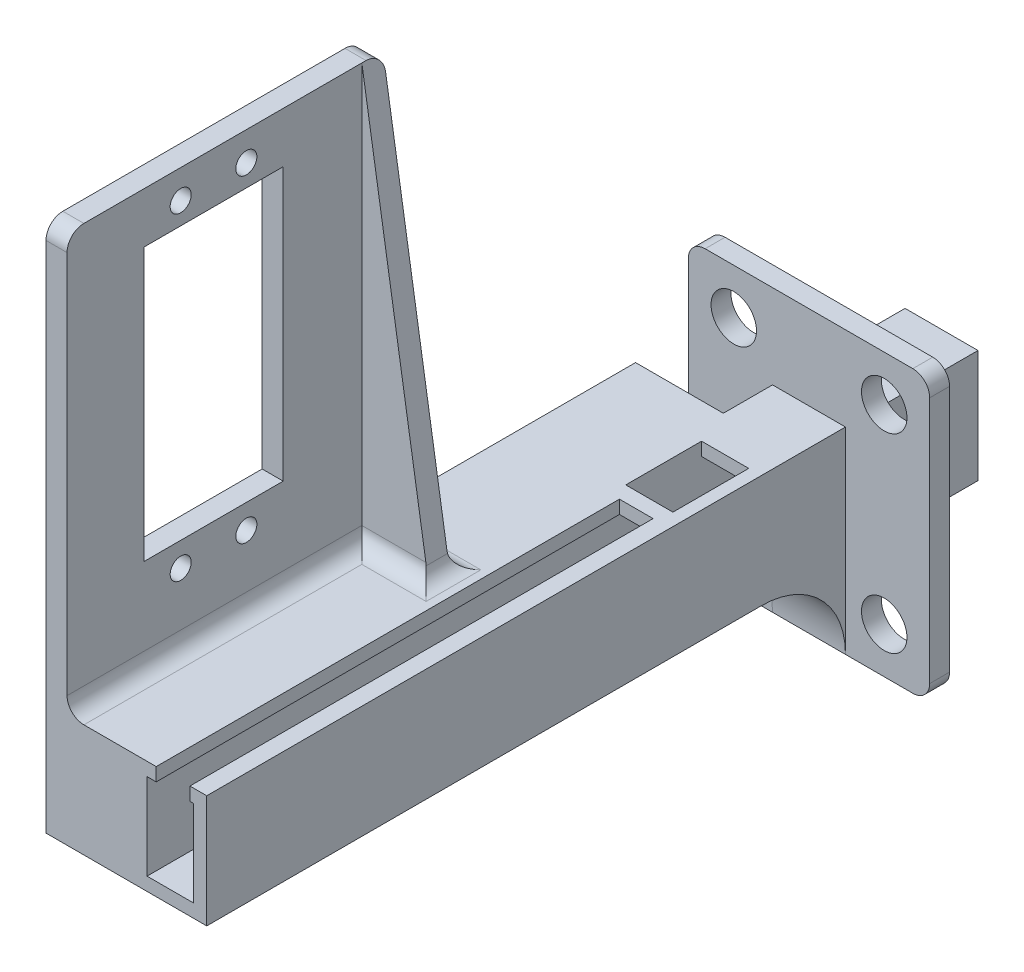
SolidWorks part; units mm, degrees
ref_plane "Front Plane" through (0, 0, 0) normal (0, 0, 1) x (1, 0, 0)
ref_plane "Top Plane" through (0, 0, 0) normal (0, 1, 0) x (1, 0, 0)
ref_plane "Right Plane" through (0, 0, 0) normal (1, 0, 0) x (0, 0, -1)
sketch "Sketch1" plane through (0, 0, 0) normal (0, 0, 1) x (1, 0, 0)
  line L1 (0, 0) -> (7, 0)
  line L2 (0, 0) -> (0, 13)
  line L3 (0, 13) -> (7, 13)
  line L4 (7, 0) -> (7, 13)
  line L5 (-2, -2) -> (9, -2)
  line L6 (-2, -2) -> (-2, 15)
  line L7 (-2, 15) -> (9, 15)
  line L8 (9, -2) -> (9, 15)
  dimension "D1" = 7
  dimension "D2" = 13
  dimension "D3" = 2
  dimension "D4" = 2
  dimension "D5" = 2
  dimension "D6" = 2
extrude "Boss-Extrude1" add sketch "Sketch1" along normal blind 76.2
sketch "Sketch2" plane through (0, 0, 0) normal (0, 0, -1) x (-1, 0, 0)
  line L1 (-9, -2) -> (2, -2)
  line L2 (-9, -2) -> (-9, 15)
  line L3 (-9, 15) -> (2, 15)
  line L4 (2, -2) -> (2, 15)
extrude "Boss-Extrude2" add sketch "Sketch2" along normal blind 2
sketch "Sketch3" plane through (0, -2, 0) normal (0, -1, 0) x (-1, 0, 0)
  line L0 (-9, 2) -> (2, 2) construction
  line L1 (-7, 0) -> (0, 0)
  line L2 (-7, 0) -> (-7, -11)
  line L3 (-7, -11) -> (0, -11)
  line L4 (0, 0) -> (0, -11)
  line L5 (2, -76.2) -> (2, 2) construction
  line L6 (-9, -76.2) -> (-9, 2) construction
  dimension "D1" = 2
  dimension "D2" = 2
  dimension "D3" = 2
  dimension "D4" = 11
extrude "Cut-Extrude1" cut sketch "Sketch3" against normal up to surface (2 mm away) up to face at (3.5, 0, 38.1)
ref_plane "Plane1" through (0, 0, 14.986) normal (0, 0, 1) x (1, 0, 0)
sketch "Sketch4" plane through (0, 0, 14.986) normal (0, 0, 1) x (1, 0, 0)
  line L2 (-2, 15) -> (9, 15)
  line L3 (-2, 15) -> (-2, -2)
  line L4 (-2, -2) -> (9, -2)
  line L5 (9, 15) -> (9, -2)
  line L6 (-12.16, 27.7) -> (19.16, 27.7)
  line L7 (-14.7, 25.16) -> (-14.7, -12.16)
  line L8 (-12.16, -14.7) -> (19.16, -14.7)
  line L9 (21.7, 25.16) -> (21.7, -12.16)
  circle A1 centre (-7.842, 20.842) radius 3.429
  circle A2 centre (14.842, 20.842) radius 3.429
  circle A3 centre (-7.842, -7.842) radius 3.429
  circle A4 centre (14.842, -7.842) radius 3.429
  arc A5 (-12.16, 27.7) -> (-14.7, 25.16) centre (-12.16, 25.16) ccw
  arc A6 (-14.7, -12.16) -> (-12.16, -14.7) centre (-12.16, -12.16) ccw
  arc A7 (19.16, -14.7) -> (21.7, -12.16) centre (19.16, -12.16) ccw
  arc A8 (21.7, 25.16) -> (19.16, 27.7) centre (19.16, 25.16) ccw
  point P3 (0, 0)
  dimension "D3" = 12.7
  dimension "D5" = 6.858
  dimension "D6" = 6.858
  dimension "D7" = 6.858
  dimension "D8" = 6.858
  dimension "D17" = 2.54
  dimension "D1" = 12.7
  dimension "D2" = 12.7
  dimension "D4" = 12.7
  dimension "D9" = 6.858
  dimension "D10" = 6.858
  dimension "D11" = 6.858
  dimension "D12" = 6.858
  dimension "D13" = 6.858
  dimension "D14" = 6.858
  dimension "D15" = 6.858
  dimension "D16" = 6.858
extrude "Boss-Extrude3" add sketch "Sketch4" along normal blind 3
sketch "Sketch6" plane through (0, 15, 0) normal (0, 1, 0) x (1, 0, 0)
  line L0 (9, -17.986) -> (-2, -17.986) construction
  line L1 (0, -30.686) -> (7.112, -30.686)
  line L2 (0, -30.686) -> (0, -42.116)
  line L3 (0, -42.116) -> (7.112, -42.116)
  line L4 (7.112, -30.686) -> (7.112, -42.116)
  line L5 (-2, -76.2) -> (-2, -17.986) construction
  dimension "D1" = 12.7
  dimension "D2" = 11.43
  dimension "D3" = 7.112
  dimension "D4" = 2
extrude "Cut-Extrude2" cut sketch "Sketch6" against normal up to surface (2 mm away) up to face at (3.5, 13, 38.1)
sketch "Sketch9" plane through (-2, 0, 0) normal (-1, 0, 0) x (0, 0, 1)
  line L1 (76.2, 15) -> (25.4, 15)
  line L2 (76.2, 15) -> (76.2, -2)
  line L3 (76.2, -2) -> (25.4, -2)
  line L4 (25.4, 15) -> (25.4, -2)
  dimension "D1" = 17
  dimension "D2" = 50.8
extrude "Boss-Extrude6" add sketch "Sketch9" along normal blind 13.24
sketch "Sketch15" plane through (0, 15, 0) normal (0, 1, 0) x (1, 0, 0)
  line L1 (6.46, -76.2) -> (1.38, -76.2)
  line L2 (6.46, -76.2) -> (6.46, -44.45)
  line L3 (6.46, -44.45) -> (1.38, -44.45)
  line L4 (1.38, -76.2) -> (1.38, -44.45)
extrude "Cut-Extrude3" cut sketch "Sketch15" against normal up to surface (2 mm away) up to face at (3.5, 13, 59.158)
sketch "Sketch16" plane through (0, 0, 76.2) normal (0, 0, 1) x (1, 0, 0)
  line L0 (6.46, 13) -> (7, 13)
  line L1 (-15.24, 15) -> (1.38, 15)
  line L2 (-15.24, 15) -> (-15.24, -2)
  line L3 (-15.24, -2) -> (9, -2)
  line L4 (9, 15) -> (9, -2)
  line L5 (0, 13) -> (1.38, 13)
  line L6 (0, 13) -> (0, 0)
  line L7 (0, 0) -> (7, 0)
  line L8 (7, 13) -> (7, 0)
  line L10 (1.38, 15) -> (1.38, 13)
  line L12 (6.46, 15) -> (6.46, 13)
  line L13 (6.46, 15) -> (9, 15)
extrude "Boss-Extrude12" add sketch "Sketch16" along normal blind 38.1
sketch "Sketch17" plane through (-15.24, 0, 0) normal (-1, 0, 0) x (0, 0, 1)
  line L1 (114.3, 15) -> (69.85, 15)
  line L2 (114.3, 15) -> (114.3, 77.9402)
  line L3 (114.3, 77.9402) -> (69.85, 77.9402)
  line L4 (69.85, 15) -> (69.85, 77.9402)
  line L5 (81.708, 70.3202) -> (102.724, 70.3202)
  line L6 (81.708, 70.3202) -> (81.708, 29.2582)
  line L7 (81.708, 29.2582) -> (102.724, 29.2582)
  line L8 (102.724, 70.3202) -> (102.724, 29.2582)
  line L9 (101.216, 29.7662) -> (95.356, 29.7662) construction
  line L10 (83.216, 70.0662) -> (101.216, 70.0662) construction
  line L11 (82.216, 30.7662) -> (82.216, 69.0662) construction
  line L12 (102.216, 69.0662) -> (102.216, 30.7662) construction
  dimension "D1" = 44.45
  dimension "D2" = 7.62
  dimension "D3" = 0.508
  dimension "D4" = 0.254
  dimension "D5" = 0.508
  dimension "D6" = 0.508
extrude "Boss-Extrude13" add sketch "Sketch17" against normal blind 3.175
sketch "Sketch19" plane through (0, 0, 69.85) normal (0, 0, -1) x (-1, 0, 0)
  line L0 (12.065, 77.9402) -> (2, 15)
  line L1 (2, 15) -> (15.24, 15)
  line L2 (15.24, 15) -> (2, 15) construction
  line L3 (15.24, 15) -> (15.24, 77.9402)
  line L4 (15.24, 77.9402) -> (12.065, 77.9402)
extrude "Boss-Extrude14" add sketch "Sketch19" along normal blind 3.175
fillet "Fillet2" radius 2.54 6 edges at (-8.62, 15, 66.675) (-2, 15, 68.2625) (-7.0325, 15, 69.85) (-12.065, 15, 92.075) (-13.6525, 77.9402, 66.675) (-13.6525, 77.9402, 114.3)
sketch "Sketch20" plane through (-12.065, 0, 0) normal (1, 0, 0) x (0, 0, -1)
  circle A0 centre (-87.266, 73.6162) radius 1.5875
  circle A1 centre (-97.166, 73.6162) radius 1.5875
  circle A2 centre (-97.166, 25.6162) radius 1.5875
  circle A3 centre (-87.266, 25.6162) radius 1.5875
  dimension "D1" = 3.175
  dimension "D2" = 3.175
  dimension "D3" = 3.175
  dimension "D4" = 3.175
extrude "Cut-Extrude4" cut sketch "Sketch20" against normal through all
fillet "Fillet3" radius 12.7 1 edges at (3.5, -2, 17.986)
